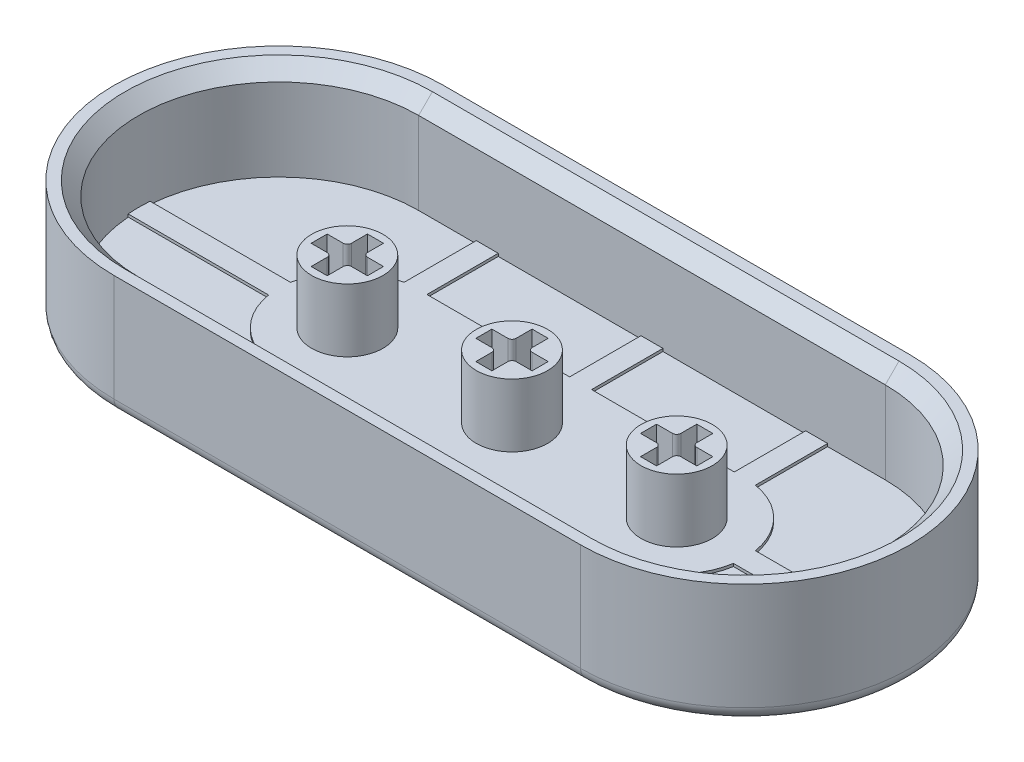
SolidWorks part; units mm, degrees
ref_plane "Front Plane" through (0, 0, 0) normal (0, 0, 1) x (1, 0, 0)
ref_plane "Top Plane" through (0, 0, 0) normal (0, 1, 0) x (1, 0, 0)
ref_plane "Right Plane" through (0, 0, 0) normal (1, 0, 0) x (0, 0, -1)
sketch "Sketch1" plane through (0, 0, 0) normal (0, 1, 0) x (1, 0, 0)
  line L0 (17, 0) -> (-17, 0) construction
  line L1 (17, -12) -> (-17, -12)
  line L2 (17, 12) -> (-17, 12)
  arc A1 (17, -12) -> (17, 12) centre (17, 0) ccw
  arc A2 (-17, 12) -> (-17, -12) centre (-17, 0) ccw
  point P5 (0, 0)
  point P10 (-29, 0)
  point P11 (29, 0)
  dimension "D2" = 12
  dimension "D3" = 58
extrude "button top" add sketch "Sketch1" along normal blind 1.8
sketch "Sketch2" plane through (0, 1.8, 0) normal (0, 1, 0) x (1, 0, 0)
  line L0 (-17, 0) -> (17, 0) construction
  line L1 (-17, 12) -> (17, 12)
  line L2 (-17, -12) -> (17, -12)
  line L3 (-17, 0) -> (17, 0) construction
  line L4 (-17, 10.2) -> (17, 10.2)
  line L5 (-17, -10.2) -> (17, -10.2)
  arc A2 (-17, 12) -> (-17, -12) centre (-17, 0) ccw
  arc A6 (17, -12) -> (17, 12) centre (17, 0) ccw
  arc A7 (17, -12) -> (17, 12) centre (17, 0) ccw construction
  arc A8 (-17, 10.2) -> (-17, -10.2) centre (-17, 0) ccw
  arc A9 (17, -10.2) -> (17, 10.2) centre (17, 0) ccw
  point P2 (0, 0)
  point P15 (0, 0)
  dimension "D1" = 1.8
extrude "button walls" add sketch "Sketch2" along normal blind 7
sketch "Sketch5" plane through (0, 1.8, 0) normal (0, 1, 0) x (1, 0, 0)
  line L0 (-12, 0) -> (12, 0) construction
  line L1 (-12, 5) -> (12, 5)
  line L2 (-12, -5) -> (12, -5)
  arc A0 (-12, 5) -> (-12, -5) centre (-12, 0) ccw
  arc A1 (12, -5) -> (12, 5) centre (12, 0) ccw
  point P3 (0, 0)
  dimension "D1" = 5
  dimension "D2" = 24
extrude "offset" add sketch "Sketch5" along normal blind 0.2
sketch "Sketch3" plane through (0, 1.8, 0) normal (0, 1, 0) x (1, 0, 0)
  line L0 (0, -2.05) -> (0, 2.05) construction
  line L1 (-2.05, 0) -> (2.05, 0) construction
  line L2 (-0.585, 0.885) -> (-0.585, 2.05)
  line L3 (-0.585, -2.05) -> (0.585, -2.05)
  line L4 (-0.585, -2.05) -> (-0.585, -0.885)
  line L5 (-0.585, 2.05) -> (0.585, 2.05)
  line L6 (0.585, -2.05) -> (0.585, -0.885)
  line L7 (-0.585, -2.05) -> (0.585, 2.05) construction
  line L8 (-0.585, 2.05) -> (0.585, -2.05) construction
  line L9 (-2.05, -0.585) -> (-0.885, -0.585)
  line L10 (-2.05, -0.585) -> (-2.05, 0.585)
  line L11 (-2.05, 0.585) -> (-0.885, 0.585)
  line L12 (2.05, -0.585) -> (2.05, 0.585)
  line L13 (-2.05, -0.585) -> (2.05, 0.585) construction
  line L14 (-2.05, 0.585) -> (2.05, -0.585) construction
  line L15 (0.885, 0.585) -> (2.05, 0.585)
  line L16 (0.585, 0.885) -> (0.585, 2.05)
  line L17 (0.885, -0.585) -> (2.05, -0.585)
  line L18 (11.415, 0.885) -> (11.415, 2.05)
  line L19 (11.415, -2.05) -> (12.585, -2.05)
  line L20 (11.415, -2.05) -> (11.415, -0.885)
  line L21 (11.415, 2.05) -> (12.585, 2.05)
  line L22 (12.585, -2.05) -> (12.585, -0.885)
  line L23 (9.95, -0.585) -> (11.115, -0.585)
  line L24 (9.95, -0.585) -> (9.95, 0.585)
  line L25 (9.95, 0.585) -> (11.115, 0.585)
  line L26 (14.05, -0.585) -> (14.05, 0.585)
  line L27 (12.885, 0.585) -> (14.05, 0.585)
  line L28 (12.585, 0.885) -> (12.585, 2.05)
  line L29 (12.885, -0.585) -> (14.05, -0.585)
  line L30 (12, -2.05) -> (12, 2.05) construction
  line L31 (9.95, 0) -> (14.05, 0) construction
  line L32 (11.415, -2.05) -> (12.585, 2.05) construction
  line L33 (11.415, 2.05) -> (12.585, -2.05) construction
  line L34 (9.95, -0.585) -> (14.05, 0.585) construction
  line L35 (9.95, 0.585) -> (14.05, -0.585) construction
  line L36 (-12.585, 0.885) -> (-12.585, 2.05)
  line L37 (-12.585, -2.05) -> (-11.415, -2.05)
  line L38 (-12.585, -2.05) -> (-12.585, -0.885)
  line L39 (-12.585, 2.05) -> (-11.415, 2.05)
  line L40 (-11.415, -2.05) -> (-11.415, -0.885)
  line L41 (-14.05, -0.585) -> (-12.885, -0.585)
  line L42 (-14.05, -0.585) -> (-14.05, 0.585)
  line L43 (-14.05, 0.585) -> (-12.885, 0.585)
  line L44 (-9.95, -0.585) -> (-9.95, 0.585)
  line L45 (-11.115, 0.585) -> (-9.95, 0.585)
  line L46 (-11.415, 0.885) -> (-11.415, 2.05)
  line L47 (-11.115, -0.585) -> (-9.95, -0.585)
  line L48 (-12, -2.05) -> (-12, 2.05) construction
  line L49 (-14.05, 0) -> (-9.95, 0) construction
  line L50 (-12.585, -2.05) -> (-11.415, 2.05) construction
  line L51 (-12.585, 2.05) -> (-11.415, -2.05) construction
  line L52 (-14.05, -0.585) -> (-9.95, 0.585) construction
  line L53 (-14.05, 0.585) -> (-9.95, -0.585) construction
  circle A0 centre (0, 0) radius 2.6
  arc A1 (-0.585, -0.885) -> (-0.885, -0.585) centre (-0.885, -0.885) ccw
  arc A2 (0.585, -0.885) -> (0.885, -0.585) centre (0.885, -0.885) cw
  arc A3 (0.885, 0.585) -> (0.585, 0.885) centre (0.885, 0.885) cw
  arc A4 (-0.585, 0.885) -> (-0.885, 0.585) centre (-0.885, 0.885) cw
  circle A5 centre (12, 0) radius 2.6
  arc A6 (11.415, -0.885) -> (11.115, -0.585) centre (11.115, -0.885) ccw
  arc A7 (12.585, -0.885) -> (12.885, -0.585) centre (12.885, -0.885) cw
  arc A8 (12.885, 0.585) -> (12.585, 0.885) centre (12.885, 0.885) cw
  arc A9 (11.415, 0.885) -> (11.115, 0.585) centre (11.115, 0.885) cw
  circle A10 centre (-12, 0) radius 2.6
  arc A11 (-12.585, -0.885) -> (-12.885, -0.585) centre (-12.885, -0.885) ccw
  arc A12 (-11.415, -0.885) -> (-11.115, -0.585) centre (-11.115, -0.885) cw
  arc A13 (-11.115, 0.585) -> (-11.415, 0.885) centre (-11.115, 0.885) cw
  arc A14 (-12.585, 0.885) -> (-12.885, 0.585) centre (-12.885, 0.885) cw
  point P2 (0, 0)
  point P6 (0, 0)
  point P9 (0, 0)
  point P22 (2.05, 0)
  point P24 (0, 2.05)
  point P29 (0.585, -0.585)
  point P32 (0.585, 0.585)
  point P40 (12, 0)
  point P43 (12, 0)
  point P69 (-12, 0)
  point P72 (-12, 0)
  dimension "D1" = 5.2
  dimension "D4" = 0.3
  dimension "D2" = 4.1
  dimension "D3" = 1.17
  dimension "D7" = 12
  dimension "D8" = 12
  dimension "D5" = 2
  dimension "D6" = 2
extrude "stem housing" add sketch "Sketch3" along normal blind 4.6 from surface starting at face at (0, 2, 0)
sketch "Sketch4" plane through (0, 1.8, 0) normal (0, 1, 0) x (1, 0, 0)
  line L0 (0, 2.6) -> (0, 10.2) construction
  line L1 (-0.8, 2.6) -> (-0.8, 10.2)
  line L2 (0.8, 2.6) -> (0.8, 10.2)
  line L3 (0, -4.84) -> (0, 4.84) construction
  line L6 (-14.6, 0) -> (-27.2, 0) construction
  line L9 (9.4, 0) -> (2.6, 0) construction
  line L12 (9.4, 0.8) -> (2.6, 0.8)
  line L15 (9.4, -0.8) -> (2.6, -0.8)
  line L18 (14.6, 0) -> (27.2, 0) construction
  line L19 (14.6, -0.8) -> (27.2, -0.8)
  line L20 (14.6, 0.8) -> (27.2, 0.8)
  line L21 (12, 2.6) -> (12, 10.2) construction
  line L22 (11.2, 2.6) -> (11.2, 10.2)
  line L23 (12.8, 2.6) -> (12.8, 10.2)
  line L24 (-12, 2.6) -> (-12, 10.2) construction
  line L25 (-12.8, 2.6) -> (-12.8, 10.2)
  line L26 (-11.2, 2.6) -> (-11.2, 10.2)
  line L27 (-14.6, -0.8) -> (-27.2, -0.8)
  line L28 (-14.6, 0.8) -> (-27.2, 0.8)
  line L29 (-4.84, 0) -> (4.84, 0) construction
  line L32 (-9.4, 0) -> (-2.6, 0) construction
  line L33 (-9.4, 0.8) -> (-2.6, 0.8)
  line L34 (-9.4, -0.8) -> (-2.6, -0.8)
  line L35 (0, -2.6) -> (0, -10.2) construction
  line L36 (-0.8, -2.6) -> (-0.8, -10.2)
  line L37 (0.8, -2.6) -> (0.8, -10.2)
  line L38 (12, -2.6) -> (12, -10.2) construction
  line L39 (11.2, -2.6) -> (11.2, -10.2)
  line L40 (12.8, -2.6) -> (12.8, -10.2)
  line L41 (-12, -2.6) -> (-12, -10.2) construction
  line L42 (-12.8, -2.6) -> (-12.8, -10.2)
  line L43 (-11.2, -2.6) -> (-11.2, -10.2)
  line L44 (17, 10.2) -> (-17, 10.2) construction
  circle A0 centre (0, 0) radius 2.6 construction
  circle A1 centre (0, 0) radius 2.6 construction
  arc A3 (-0.8, 2.6) -> (0.8, 2.6) centre (0, 2.6) ccw
  arc A4 (0.8, 10.2) -> (-0.8, 10.2) centre (0, 10.2) ccw
  arc A15 (9.4, 0.8) -> (9.4, -0.8) centre (9.4, 0) cw
  arc A16 (2.6, -0.8) -> (2.6, 0.8) centre (2.6, 0) cw
  arc A17 (14.6, -0.8) -> (14.6, 0.8) centre (14.6, 0) cw
  arc A18 (27.2, 0.8) -> (27.2, -0.8) centre (27.2, 0) cw
  arc A19 (11.2, 2.6) -> (12.8, 2.6) centre (12, 2.6) ccw
  arc A20 (12.8, 10.2) -> (11.2, 10.2) centre (12, 10.2) ccw
  arc A21 (-12.8, 2.6) -> (-11.2, 2.6) centre (-12, 2.6) ccw
  arc A22 (-11.2, 10.2) -> (-12.8, 10.2) centre (-12, 10.2) ccw
  circle A23 centre (-12, 0) radius 2.6 construction
  circle A24 centre (-12, 0) radius 2.6 construction
  arc A25 (-17, 10.2) -> (-17, -10.2) centre (-17, 0) ccw construction
  arc A26 (-14.6, -0.8) -> (-14.6, 0.8) centre (-14.6, 0) ccw
  arc A27 (-27.2, 0.8) -> (-27.2, -0.8) centre (-27.2, 0) ccw
  arc A33 (-9.4, 0.8) -> (-9.4, -0.8) centre (-9.4, 0) ccw
  arc A34 (-2.6, -0.8) -> (-2.6, 0.8) centre (-2.6, 0) ccw
  arc A35 (-0.8, -2.6) -> (0.8, -2.6) centre (0, -2.6) cw
  arc A36 (0.8, -10.2) -> (-0.8, -10.2) centre (0, -10.2) cw
  arc A37 (11.2, -2.6) -> (12.8, -2.6) centre (12, -2.6) cw
  arc A38 (12.8, -10.2) -> (11.2, -10.2) centre (12, -10.2) cw
  arc A39 (-12.8, -2.6) -> (-11.2, -2.6) centre (-12, -2.6) cw
  arc A40 (-11.2, -10.2) -> (-12.8, -10.2) centre (-12, -10.2) cw
  point P9 (0, 6.4)
  point P19 (6, 0)
  point P33 (20.9, 0)
  point P40 (12, 6.4)
  point P47 (-12, 6.4)
  point P55 (0, -6.4)
  point P59 (-20.9, 0)
  point P69 (12, -6.4)
  point P76 (-12, -6.4)
  point P81 (-6, 0)
  dimension "D1" = 1.6
  dimension "D3" = 2
  dimension "D4" = 12
  dimension "D5" = 12
  dimension "D2" = 2
extrude "spokes" add sketch "Sketch4" along normal up to surface (0.2 mm away) up to face at (12, 2, 2.6)
fillet "Fillet1" radius 1 4 edges at (0, 0, -12) (-29, 0, 0) (0, 0, 12) (29, 0, 0)
chamfer "Chamfer1" distance 1 angle 45 4 edges at (0, 8.8, 10.2) (27.2, 8.8, 0) (-27.2, 8.8, 0) (0, 8.8, -10.2)
